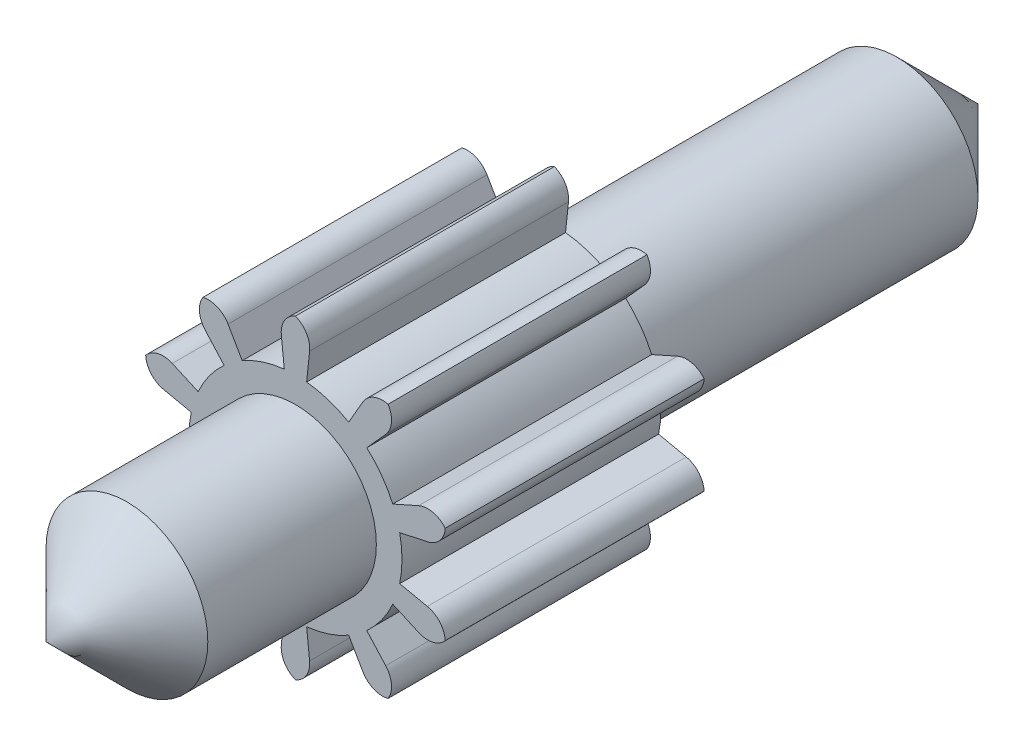
SolidWorks part; units mm, degrees
material "AISI 316 Stainless Steel Sheet (SS)"
ref_plane "Front Plane" through (0, 0, 0) normal (0, 0, 1) x (1, 0, 0)
ref_plane "Top Plane" through (0, 0, 0) normal (0, 1, 0) x (1, 0, 0)
ref_plane "Right Plane" through (0, 0, 0) normal (1, 0, 0) x (0, 0, -1)
sketch "Sketch1" plane through (0, 0, 0) normal (0, 0, 1) x (1, 0, 0)
  line L0 (0, 0) -> (0, 2.1489) construction
  line L1 (-0.1035, 0.9821) -> (-0.1311, 1.2431)
  line L2 (0.1035, 0.9821) -> (0.1311, 1.2431)
  line L3 (0.661, 0.7336) -> (0.8367, 0.9287)
  line L4 (0.4935, 0.8554) -> (0.6246, 1.0827)
  line L5 (0.966, 0.205) -> (1.2228, 0.2595)
  line L6 (0.902, 0.4019) -> (1.1418, 0.5088)
  line L7 (0.902, -0.4019) -> (1.1418, -0.5088)
  line L8 (0.966, -0.205) -> (1.2228, -0.2595)
  line L9 (0.4935, -0.8554) -> (0.6246, -1.0827)
  line L10 (0.661, -0.7336) -> (0.8367, -0.9287)
  line L11 (-0.1035, -0.9821) -> (-0.1311, -1.2431)
  line L12 (0.1035, -0.9821) -> (0.1311, -1.2431)
  line L13 (-0.661, -0.7336) -> (-0.8367, -0.9287)
  line L14 (-0.4935, -0.8554) -> (-0.6246, -1.0827)
  line L15 (-0.966, -0.205) -> (-1.2228, -0.2595)
  line L16 (-0.902, -0.4019) -> (-1.1418, -0.5088)
  line L17 (-0.902, 0.4019) -> (-1.1418, 0.5088)
  line L18 (-0.966, 0.205) -> (-1.2228, 0.2595)
  line L19 (-0.4935, 0.8554) -> (-0.6246, 1.0827)
  line L20 (-0.661, 0.7336) -> (-0.8367, 0.9287)
  arc A0 (-0.1035, 0.9821) -> (-0.4935, 0.8554) centre (0, 0) ccw
  arc A1 (-0.661, 0.7336) -> (-0.902, 0.4019) centre (0, 0) ccw
  arc A2 (0.4935, 0.8554) -> (0.1035, 0.9821) centre (0, 0) ccw
  arc A3 (-0.1311, 1.2431) -> (0, 1.46) centre (0.0775, 1.2651) cw
  arc A4 (0.1311, 1.2431) -> (0, 1.46) centre (-0.0775, 1.2651) ccw
  arc A5 (0.6246, 1.0827) -> (0.8582, 1.1812) centre (0.8063, 0.9779) cw
  arc A6 (0.8367, 0.9287) -> (0.8582, 1.1812) centre (0.6809, 1.0691) ccw
  arc A7 (1.1418, 0.5088) -> (1.3885, 0.4512) centre (1.2271, 0.3172) cw
  arc A8 (1.2228, 0.2595) -> (1.3885, 0.4512) centre (1.1792, 0.4647) ccw
  arc A9 (1.2228, -0.2595) -> (1.3885, -0.4512) centre (1.1792, -0.4647) cw
  arc A10 (1.1418, -0.5088) -> (1.3885, -0.4512) centre (1.2271, -0.3172) ccw
  arc A11 (0.8367, -0.9287) -> (0.8582, -1.1812) centre (0.6809, -1.0691) cw
  arc A12 (0.6246, -1.0827) -> (0.8582, -1.1812) centre (0.8063, -0.9779) ccw
  arc A13 (0.1311, -1.2431) -> (0, -1.46) centre (-0.0775, -1.2651) cw
  arc A14 (-0.1311, -1.2431) -> (0, -1.46) centre (0.0775, -1.2651) ccw
  arc A15 (-0.6246, -1.0827) -> (-0.8582, -1.1812) centre (-0.8063, -0.9779) cw
  arc A16 (-0.8367, -0.9287) -> (-0.8582, -1.1812) centre (-0.6809, -1.0691) ccw
  arc A17 (-1.1418, -0.5088) -> (-1.3885, -0.4512) centre (-1.2271, -0.3172) cw
  arc A18 (-1.2228, -0.2595) -> (-1.3885, -0.4512) centre (-1.1792, -0.4647) ccw
  arc A19 (-1.2228, 0.2595) -> (-1.3885, 0.4512) centre (-1.1792, 0.4647) cw
  arc A20 (-1.1418, 0.5088) -> (-1.3885, 0.4512) centre (-1.2271, 0.3172) ccw
  arc A21 (-0.8367, 0.9287) -> (-0.8582, 1.1812) centre (-0.6809, 1.0691) cw
  arc A22 (-0.6246, 1.0827) -> (-0.8582, 1.1812) centre (-0.8063, 0.9779) ccw
  arc A23 (0.902, 0.4019) -> (0.661, 0.7336) centre (0, 0) ccw
  arc A24 (0.966, -0.205) -> (0.966, 0.205) centre (0, 0) ccw
  arc A25 (0.661, -0.7336) -> (0.902, -0.4019) centre (0, 0) ccw
  arc A26 (0.1035, -0.9821) -> (0.4935, -0.8554) centre (0, 0) ccw
  arc A27 (-0.4935, -0.8554) -> (-0.1035, -0.9821) centre (0, 0) ccw
  arc A28 (-0.902, -0.4019) -> (-0.661, -0.7336) centre (0, 0) ccw
  arc A29 (-0.966, 0.205) -> (-0.966, -0.205) centre (0, 0) ccw
  circle A30 centre (0, 0) radius 0.75
  point P78 (0, 0)
  dimension "D1" = 2.92
  dimension "D2" = 1.975
  dimension "D3" = 1.5
  dimension "D4" = 10
extrude "Boss-Extrude1" add sketch "Sketch1" along normal blind 2.4
extrude "Boss-Extrude2" add sketch "Sketch1<2>" along normal blind 4.7124 and the other way blind 3.927 contours A30 region at (0, 0, 0)
sketch "Sketch1<2>" plane through (0, 0, 0) normal (0, 0, 1) x (1, 0, 0) same geometry as "Sketch1"
chamfer "Chamfer1" distance 0.75 angle 45 2 edges at (0.75, 0, -3.927) (0.75, 0, 4.7124)
